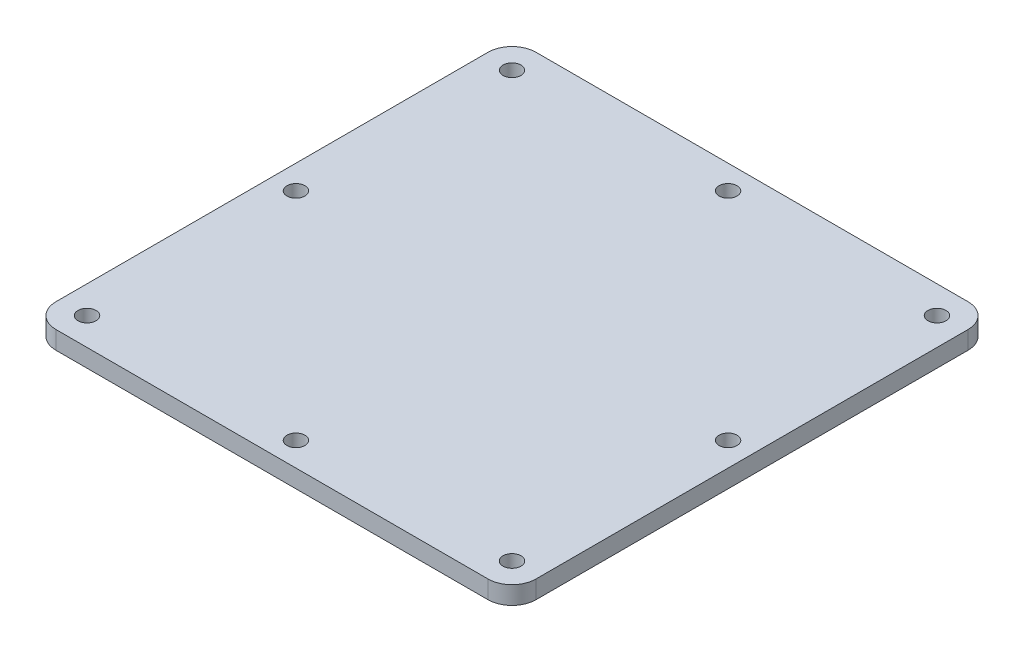
SolidWorks part; units mm, degrees
material "PMMA"
ref_plane "前视基准面" through (0, 0, 0) normal (0, 0, 1) x (1, 0, 0)
ref_plane "上视基准面" through (0, 0, 0) normal (0, 1, 0) x (1, 0, 0)
ref_plane "右视基准面" through (0, 0, 0) normal (1, 0, 0) x (0, 0, -1)
sketch "草图1" plane through (0, 0, 0) normal (0, 1, 0) x (1, 0, 0)
  line L1 (-40, -40) -> (40, -40)
  line L2 (-40, -40) -> (-40, 40)
  line L3 (-40, 40) -> (40, 40)
  line L4 (40, -40) -> (40, 40)
  line L5 (-40, -40) -> (40, 40) construction
  line L6 (-40, 40) -> (40, -40) construction
  circle A0 centre (0, -36) radius 1.5
  circle A1 centre (-35.4038, -35.4038) radius 1.5
  point P0 (0, 0)
  dimension "D3" = 3
  dimension "D4" = 3
  dimension "D1" = 80
  dimension "D2" = 80
  dimension "D5" = 4
  dimension "D6" = 6.5
sketch "草图2" plane through (0, 0, 0) normal (0, 1, 0) x (1, 0, 0)
  line L1 (-40, 40) -> (40, 40)
  line L2 (-40, 40) -> (-40, -40)
  line L3 (-40, -40) -> (40, -40)
  line L4 (40, 40) -> (40, -40)
  line L5 (-40, 40) -> (40, -40) construction
  line L6 (-40, -40) -> (40, 40) construction
  point P0 (0, 0)
extrude "凸台-拉伸1" add sketch "草图2" along normal blind 3
sketch "草图3" plane through (0, 0, 0) normal (0, 1, 0) x (1, 0, 0)
  circle A0 centre (0, -36) radius 1.5
  circle A1 centre (-35.4038, -35.4038) radius 1.5
extrude "切除-拉伸1" cut sketch "草图3" along normal blind 3
ref_axis "基准轴1" through (0, 3.15, 0) along (0, -1, 0)
pattern_circular "阵列(圆周)1" count 4 over 360 about axis through (0, 3.15, 0) along (0, -1, 0) of "切除-拉伸1"
fillet "圆角1" radius 4 4 edges at (40, 1.5, -40) (40, 1.5, 40) (-40, 1.5, -40) (-40, 1.5, 40)
